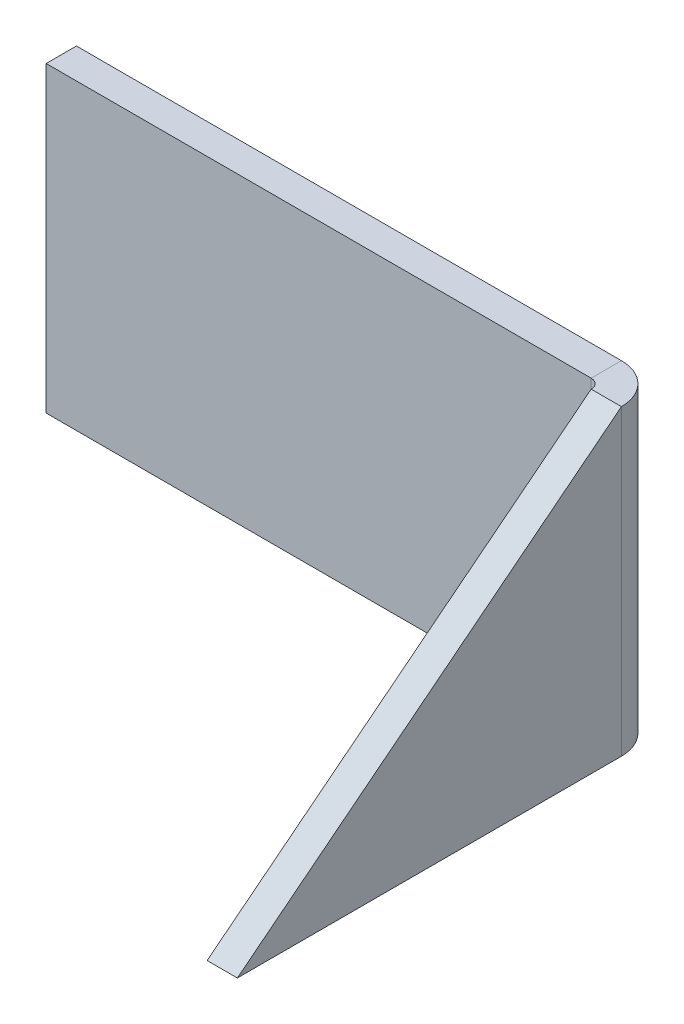
SolidWorks part; units mm, degrees
note: The reader was unsure of these and kept them because the rebuilt part matched: flange length of "Edge-Flange1".
material "6061-T6 (SS)"
ref_plane "X-Y Datum" through (0, 0, 0) normal (0, 0, 1) x (1, 0, 0)
ref_plane "X-Z Datum" through (0, 0, 0) normal (0, 1, 0) x (1, 0, 0)
ref_plane "Y-Z Datum" through (0, 0, 0) normal (1, 0, 0) x (0, 0, -1)
sketch "Sketch2" plane through (0, 0, 0) normal (0, 0, 1) x (1, 0, 0)
  line L1 (-28.575, 15.875) -> (28.575, 15.875)
  line L2 (-28.575, 15.875) -> (-28.575, -15.875)
  line L3 (-28.575, -15.875) -> (28.575, -15.875)
  line L4 (28.575, 15.875) -> (28.575, -15.875)
  line L5 (-28.575, 15.875) -> (28.575, -15.875) construction
  line L6 (-28.575, -15.875) -> (28.575, 15.875) construction
  point P0 (0, 0)
  dimension "D1" = 31.75
  dimension "D2" = 57.15
base flange "Base-Flange1" sketch "Sketch2" thickness 3.175 reverse thickness direction yes parameters "D1"=1
edge flange "Edge-Flange1" sketch "Sketch9" flange angle 90 flange length 44.45 flange position bend outside bend radius 1 thickness 3.175 relief rectangular parameters "D6"=0
sketch "Sketch9" plane through (28.575, 0, 3.175) normal (1, 0, 0) x (0, 1, 0)
  line L2 (-15.875, 0) -> (-15.875, 41.275)
  line L3 (-15.875, 41.275) -> (15.875, 41.275)
  line L4 (15.875, 41.275) -> (15.875, 0)
  line L7 (-15.875, 0) -> (15.875, 0) construction
  line L8 (-15.875, 0) -> (15.875, 0)
bend "EdgeBend1" bend radius 1 bend angle 90 parameters "D5"=1
sketch "Sketch10" plane through (32.75, 0, 0) normal (1, 0, 0) x (0, 0, -1)
  line L0 (-4.175, 15.875) -> (-44.45, -15.875)
  line L1 (-44.45, 15.875) -> (-44.45, -15.875) construction
  line L3 (-44.45, -15.875) -> (-4.175, -15.875) construction
  line L7 (-4.175, -15.875) -> (-4.175, 15.875)
  line L8 (-4.175, 15.875) -> (-44.45, 15.875)
  line L9 (-44.45, 15.875) -> (-44.45, -15.875)
  line L10 (-44.45, -15.875) -> (-4.175, -15.875)
  line L12 (-4.175, 15.875) -> (-44.45, 15.875)
  line L13 (-44.45, 15.875) -> (-44.45, -15.875)
  dimension "D1" = 0
extrude "Cut-Extrude1" cut sketch "Sketch10" against normal blind 3.175 normal cut yes
mirror "Mirror1" [suppressed] about plane through (0, 0, 0) normal (1, 0, 0)
bend "MirrorBend1" bend radius 1 bend angle 90 parameters "D5"=2
sketch "Sketch11" [suppressed] plane through (32.75, 0, 0) normal (1, 0, 0) x (0, 0, -1)
  line L0 (-4.175, -15.875) -> (-44.45, 15.875)
extrude "Cut-Extrude2" [suppressed] cut sketch "Sketch11" against normal blind 3.175 and the other way through all
sketch "Bend-Lines1" [suppressed] plane through (0, 0, 0) normal (0, 1, 0) x (1, 0, 0)
sketch "Bounding-Box1" [suppressed] plane through (0, 0, 0) normal (0, 1, 0) x (1, 0, 0)
sheet metal parameters "Sheet-Metal1" thickness 3.175 parameters "D1"=1
flat pattern "Flat-Pattern1" [suppressed]
sketch "Bend-Lines2" plane through (0, 0, 0) normal (0, 1, 0) x (1, 0, 0)
sketch3d "Bounding-Box2" [suppressed]
  line L0 (-63.5, -15.875, 0) -> (63.5, -15.875, 0) construction
  line L1 (-63.5, 15.875, 0) -> (63.5, 15.875, 0) construction
  line L2 (-63.5, -15.875, 0) -> (-63.5, 15.875, 0) construction
  line L3 (63.5, -15.875, 0) -> (63.5, 15.875, 0) construction
sheet metal parameters "Sheet-Metal2" thickness 3.175 parameters "D1"=1
flat pattern "Flat-Pattern1"
sketch "Bend-Lines2" plane through (0, 0, 0) normal (0, 0, -1) x (-1, 0, 0)
  line L0 (-30.6072, 15.875) -> (-30.6072, -15.875) construction
  line L1 (-30.6072, 15.875) -> (-30.6072, -15.875) construction
sketch3d "Bounding-Box2" [suppressed]
  line L0 (28.575, -15.875, 0) -> (-72.9144, -15.875, 0) construction
  line L1 (28.575, 15.875, 0) -> (-72.9144, 15.875, 0) construction
  line L2 (28.575, -15.875, 0) -> (28.575, 15.875, 0) construction
  line L3 (-72.9144, -15.875, 0) -> (-72.9144, 15.875, 0) construction
bend of the flat pattern "Flatten-<EdgeBend1>1"
sheet metal parameters "Sheet-Metal5" thickness 3.175 parameters "D1"=1
flat pattern "Flat-Pattern1"
sketch "Bend-Lines2" plane through (0, 0, 0) normal (0, 0, -1) x (-1, 0, 0)
  line L0 (-30.6072, 15.875) -> (-30.6072, -15.875) construction
  line L1 (-30.6072, 15.875) -> (-30.6072, -15.875) construction
  line L2 (30.6072, -15.875) -> (30.6072, 15.875) construction
  line L3 (30.6072, -15.875) -> (30.6072, 15.875) construction
sketch3d "Bounding-Box2" [suppressed]
  line L0 (72.9144, -15.875, 0) -> (-72.9144, -15.875, 0) construction
  line L1 (72.9144, 15.875, 0) -> (-72.9144, 15.875, 0) construction
  line L2 (72.9144, -15.875, 0) -> (72.9144, 15.875, 0) construction
  line L3 (-72.9144, -15.875, 0) -> (-72.9144, 15.875, 0) construction
bend of the flat pattern "Flatten-<EdgeBend1>1"
bend of the flat pattern "Flatten-<MirrorBend1>1"
sheet metal parameters "Sheet-Metal7" thickness 3.175 parameters "D1"=1
flat pattern "Flat-Pattern1"
sketch "Bend-Lines2" plane through (0, 0, 0) normal (0, 0, -1) x (-1, 0, 0)
  line L0 (-30.6072, 15.875) -> (-30.6072, -15.875) construction
  line L1 (-30.6072, 15.875) -> (-30.6072, -15.875) construction
sketch3d "Bounding-Box2" [suppressed]
  line L0 (28.575, -15.875, 0) -> (-72.9144, -15.875, 0) construction
  line L1 (28.575, 15.875, 0) -> (-72.9144, 15.875, 0) construction
  line L2 (28.575, -15.875, 0) -> (28.575, 15.875, 0) construction
  line L3 (-72.9144, -15.875, 0) -> (-72.9144, 15.875, 0) construction
bend of the flat pattern "Flatten-<EdgeBend1>1"
sheet metal parameters "Sheet-Metal8" thickness 3.175 parameters "D1"=1
flat pattern "Flat-Pattern1"
sketch "Bend-Lines2" plane through (0, 0, 0) normal (0, 0, -1) x (-1, 0, 0)
  line L0 (-30.6072, 15.875) -> (-30.6072, -15.875) construction
  line L1 (-30.6072, 15.875) -> (-30.6072, -15.875) construction
sketch3d "Bounding-Box2" [suppressed]
  line L0 (28.575, -15.875, 0) -> (-72.9144, -15.875, 0) construction
  line L1 (28.575, 15.875, 0) -> (-72.9144, 15.875, 0) construction
  line L2 (28.575, -15.875, 0) -> (28.575, 15.875, 0) construction
  line L3 (-72.9144, -15.875, 0) -> (-72.9144, 15.875, 0) construction
bend of the flat pattern "Flatten-<EdgeBend1>1"
